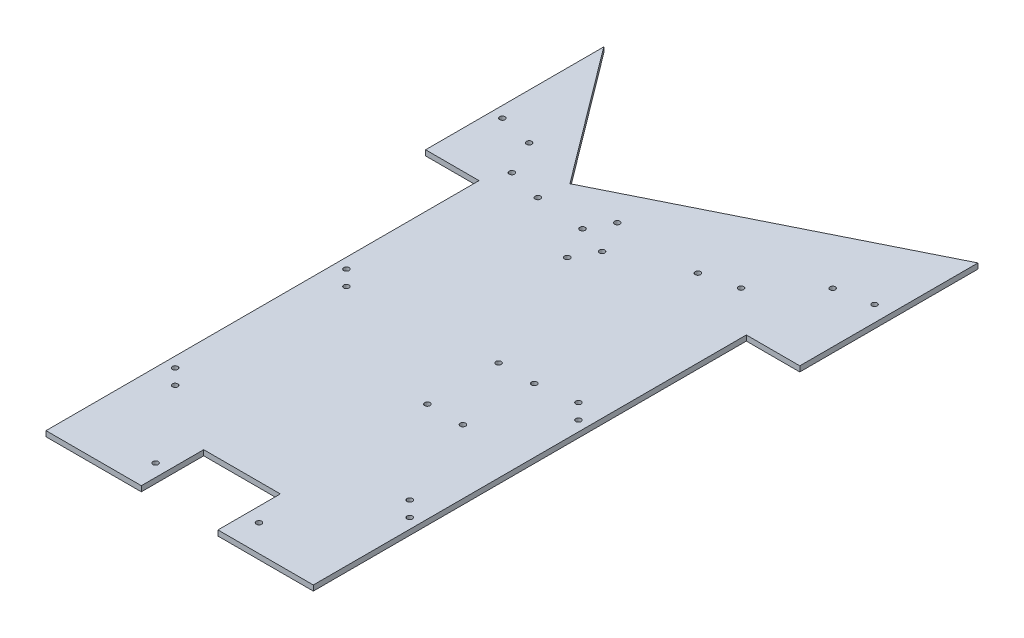
SolidWorks part; units mm, degrees
ref_plane "Front Plane" through (0, 0, 0) normal (0, 0, 1) x (1, 0, 0)
ref_plane "Top Plane" through (0, 0, 0) normal (0, 1, 0) x (1, 0, 0)
ref_plane "Right Plane" through (0, 0, 0) normal (1, 0, 0) x (0, 0, -1)
sketch "Sketch1" plane through (0, 0, 0) normal (0, 1, 0) x (1, 0, 0)
  line L0 (0, -1.65) -> (0, 1.65) construction
  line L2 (-75, -100) -> (-75, 100)
  line L3 (-75, 100) -> (75, 100)
  line L4 (75, -100) -> (75, 100)
  line L5 (-75, -100) -> (75, 100) construction
  line L6 (-75, 100) -> (75, -100) construction
  line L8 (-21.5, -100) -> (-21.5, -65)
  line L9 (-21.5, -65) -> (21.5, -65)
  line L10 (21.5, -100) -> (21.5, -65)
  line L11 (-75, -100) -> (-21.5, -100)
  line L12 (21.5, -100) -> (75, -100)
  circle A0 centre (-69.2426, 62.7961) radius 1.5
  circle A1 centre (-60.7574, 54.3108) radius 1.5
  circle A2 centre (60.7574, 63.0348) radius 1.5
  circle A3 centre (69.2426, 54.5495) radius 1.5
  circle A4 centre (-69.2426, -33.2742) radius 1.5
  circle A5 centre (-60.7574, -41.7595) radius 1.5
  circle A6 centre (60.7574, -31.6419) radius 1.5
  circle A7 centre (69.2426, -40.1271) radius 1.5
  circle A8 centre (19.1, 59.876) radius 1.5
  circle A10 centre (39.1, 19.876) radius 1.5
  circle A11 centre (19.1, 19.876) radius 1.5
  circle A12 centre (39.1, 59.876) radius 1.5
  circle A13 centre (-28.5, -85) radius 1.5
  circle A14 centre (29.5, -85) radius 1.5
  point P0 (0, 0)
  point P46 (0, -65)
  dimension "D5" = 3
  dimension "D6" = 3
  dimension "D11" = 58
  dimension "D1" = 150
  dimension "D2" = 200
  dimension "D3" = 35
  dimension "D4" = 43
  dimension "D7" = 15
  dimension "D8" = 15
  dimension "D9" = 8
extrude "Boss-Extrude1" add sketch "Sketch1" along normal blind 3
sketch "Sketch2" plane through (0, 3, 0) normal (0, 1, 0) x (1, 0, 0)
  line L8 (-75, 100) -> (-75, 143)
  line L9 (-75, 143) -> (-105, 143)
  line L10 (-105, 143) -> (-105, 243)
  line L11 (-105, 243) -> (-48, 167)
  line L12 (-48, 167) -> (105, 243)
  line L13 (105, 243) -> (105, 143)
  line L14 (105, 143) -> (75, 143)
  line L15 (75, 143) -> (75, 100)
  line L20 (-75, 100) -> (75, 100)
  circle A0 centre (-12.8714, 130.3772) radius 1.5
  circle A1 centre (-6.0318, 143.0744) radius 1.5
  circle A2 centre (-15.7372, 161.3276) radius 1.5
  circle A3 centre (-22.5768, 148.6304) radius 1.5
  circle A4 centre (31.34, 159.4445) radius 1.5
  circle A5 centre (50.7426, 164.2965) radius 1.5
  circle A6 centre (76.5366, 189.8832) radius 1.5
  circle A7 centre (96.1557, 193.7679) radius 1.5
  circle A8 centre (-50.2701, 151.2364) radius 1.5
  circle A9 centre (-69.6726, 156.0884) radius 1.5
  circle A10 centre (-79.3212, 175.4165) radius 1.5
  circle A11 centre (-98.8125, 179.8985) radius 1.5
  dimension "D2" = 100
  dimension "D3" = 27
  dimension "D4" = 30
  dimension "D1" = 43
  dimension "D5" = 24
extrude "Boss-Extrude3" add sketch "Sketch2" against normal blind 3
